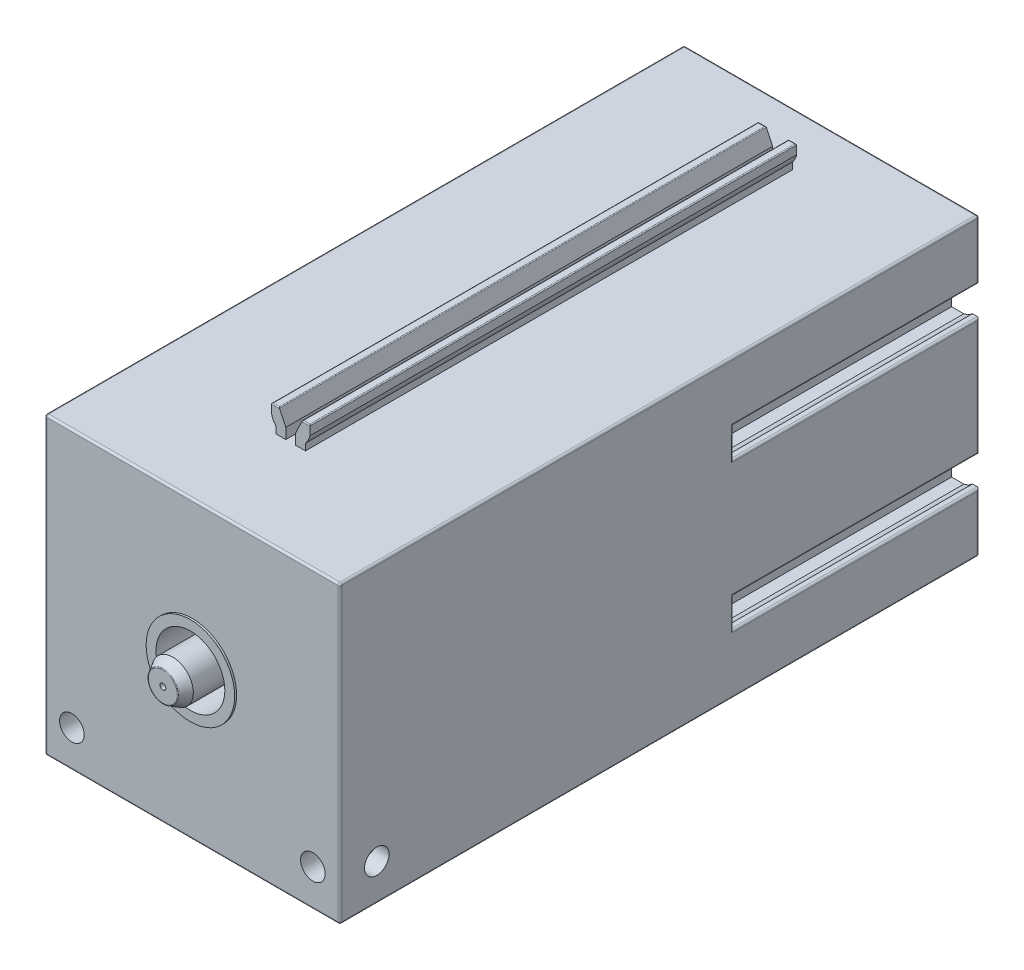
SolidWorks part; units mm, degrees
ref_plane "前视基准面" through (0, 0, 0) normal (0, 0, 1) x (1, 0, 0)
ref_plane "上视基准面" through (0, 0, 0) normal (0, 1, 0) x (1, 0, 0)
ref_plane "右视基准面" through (0, 0, 0) normal (1, 0, 0) x (0, 0, -1)
sketch "草图1" plane through (0, 0, 0) normal (0, 0, 1) x (1, 0, 0)
  line L1 (-15, 0) -> (15, 0)
  line L2 (-15, 0) -> (-15, 30)
  line L3 (-15, 30) -> (15, 30)
  line L4 (15, 0) -> (15, 30)
extrude "凸台-拉伸1" add sketch "草图1" against normal blind 65
sketch "草图2" plane through (0, 0, -65) normal (0, 0, -1) x (-1, 0, 0)
  line L0 (-9, 0.6771) -> (-9, 0)
  line L1 (15, 0) -> (-15, 0) construction
  line L2 (0, -2.0675) -> (0, 3.9748) construction
  line L3 (-6, 0.6771) -> (-6, 0)
  line L4 (-6, 0) -> (-9, 0)
  line L5 (-9.45, 2.8) -> (-5.55, 2.8)
  line L6 (-9.45, 2.8) -> (-9.45, 1.5556)
  line L7 (5.55, 2.8) -> (5.55, 1.5556)
  line L8 (-5.55, 2.8) -> (-5.55, 1.5556)
  line L9 (9.45, 2.8) -> (9.45, 1.5556)
  line L10 (9.45, 2.8) -> (5.55, 2.8)
  line L11 (6, 0) -> (9, 0)
  line L12 (6, 0.6771) -> (6, 0)
  line L13 (9, 0.6771) -> (9, 0)
  arc A0 (9.45, 1.5556) -> (9, 0.6771) centre (7.5, 2) cw
  arc A1 (-6, 0.6771) -> (-5.55, 1.5556) centre (-7.5, 2) ccw
  arc A2 (-9.45, 1.5556) -> (-9, 0.6771) centre (-7.5, 2) ccw
  arc A3 (6, 0.6771) -> (5.55, 1.5556) centre (7.5, 2) cw
extrude "切除-拉伸1" cut sketch "草图2" against normal blind 54
sketch "草图3" plane through (0, 0, -65) normal (0, 0, -1) x (-1, 0, 0)
  line L0 (-14.3229, 9) -> (-15, 9)
  line L1 (-15, 0) -> (-15, 30) construction
  line L2 (-15, 6) -> (-14.3229, 6)
  line L3 (-12.2, 9.45) -> (-12.2, 5.55)
  line L4 (-15, 9) -> (-15, 6)
  line L5 (-12.2, 5.55) -> (-13.4444, 5.55)
  line L6 (-12.2, 9.45) -> (-13.4444, 9.45)
  line L8 (-12.2, 20.55) -> (-13.4444, 20.55)
  line L9 (-12.2, 24.45) -> (-13.4444, 24.45)
  line L10 (-15, 21) -> (-15, 24)
  line L11 (-12.2, 20.55) -> (-12.2, 24.45)
  line L12 (-15, 24) -> (-14.3229, 24)
  line L13 (-14.3229, 21) -> (-15, 21)
  line L15 (14.3229, 21) -> (15, 21)
  line L16 (15, 24) -> (14.3229, 24)
  line L17 (12.2, 20.55) -> (12.2, 24.45)
  line L18 (15, 21) -> (15, 24)
  line L19 (12.2, 24.45) -> (13.4444, 24.45)
  line L20 (12.2, 20.55) -> (13.4444, 20.55)
  line L21 (12.2, 9.45) -> (13.4444, 9.45)
  line L22 (12.2, 5.55) -> (13.4444, 5.55)
  line L23 (15, 9) -> (15, 6)
  line L24 (12.2, 9.45) -> (12.2, 5.55)
  line L25 (15, 6) -> (14.3229, 6)
  line L26 (14.3229, 9) -> (15, 9)
  arc A0 (-14.3229, 6) -> (-13.4444, 5.55) centre (-13, 7.5) ccw
  arc A1 (-13.4444, 9.45) -> (-14.3229, 9) centre (-13, 7.5) ccw
  arc A2 (-13.4444, 20.55) -> (-14.3229, 21) centre (-13, 22.5) cw
  arc A3 (-14.3229, 24) -> (-13.4444, 24.45) centre (-13, 22.5) cw
  arc A4 (14.3229, 24) -> (13.4444, 24.45) centre (13, 22.5) ccw
  arc A5 (13.4444, 20.55) -> (14.3229, 21) centre (13, 22.5) ccw
  arc A6 (13.4444, 9.45) -> (14.3229, 9) centre (13, 7.5) cw
  arc A7 (14.3229, 6) -> (13.4444, 5.55) centre (13, 7.5) cw
extrude "切除-拉伸2" cut sketch "草图3" against normal blind 25
sketch "草图5" plane through (0, 0, -65) normal (0, 0, -1) x (-1, 0, 0)
  line L0 (-1.5, 30.6771) -> (-1.5, 30)
  line L1 (-15, 30) -> (15, 30) construction
  line L2 (1.5, 30) -> (1.5, 30.6771)
  line L3 (-1.95, 32.5) -> (-1.1658, 32.5)
  line L4 (-1.95, 32.5) -> (-1.95, 31.5556)
  line L5 (1.95, 32.5) -> (1.95, 31.5556)
  line L6 (-1.5, 30) -> (-0.5, 30)
  line L7 (-0.5, 30) -> (-0.5, 31.0723)
  line L8 (0.5, 30) -> (0.5, 31.0723)
  line L9 (-0.5, 31.0723) -> (-1.1658, 32.5)
  line L10 (0.5, 31.0723) -> (1.1658, 32.5)
  line L11 (1.1658, 32.5) -> (1.95, 32.5)
  line L12 (0.5, 30) -> (1.5, 30)
  arc A1 (-1.95, 31.5556) -> (-1.5, 30.6771) centre (0, 32) ccw
  arc A2 (1.5, 30.6771) -> (1.95, 31.5556) centre (0, 32) ccw
extrude "凸台-拉伸2" add sketch "草图5" against normal blind 49.5 from offset 5.5 offset against normal yes
fillet "圆角1" radius 0.1 8 edges at (-1.1658, 32.5, -34.75) (-1.5579, 32.5, -10) (-1.95, 32.5, -34.75) (-1.5579, 32.5, -59.5) (1.95, 32.5, -34.75) (1.5579, 32.5, -10) (1.1658, 32.5, -34.75) (1.5579, 32.5, -59.5)
sketch "草图6" plane through (0, 0, 0) normal (0, 0, 1) x (1, 0, 0)
  circle A0 centre (0, 15) radius 3.5
extrude "切除-拉伸3" cut sketch "草图6" against normal blind 5
sketch "草图7" plane through (0, 0, 0) normal (0, 0, 1) x (1, 0, 0)
  circle A0 centre (0, 15) radius 4.5
  circle A1 centre (0, 15) radius 3.5
extrude "凸台-拉伸3" add sketch "草图7" along normal blind 0.2
sketch "草图8" plane through (0, 0, -5) normal (0, 0, 1) x (1, 0, 0)
  circle A0 centre (0, 15) radius 2.1
extrude "凸台-拉伸4" add sketch "草图8" along normal blind 8
sketch "草图9" plane through (0, 0, 3) normal (0, 0, 1) x (1, 0, 0)
  circle A0 centre (0, 15) radius 0.3
extrude "切除-拉伸4" cut sketch "草图9" against normal blind 8
chamfer "倒角1" distance 1 angle 30 1 edges at (2.1, 15, 3) first distance on face at (2.1, 15, 3)
fillet "圆角2" radius 0.1 1 edges at (1.5226, 15, 3)
fillet "圆角3" radius 0.2 36 edges at (-12, 0, -65) (0, 0, 0) (12, 0, -65) (9, 0, -38) (7.5, 0, -11) (6, 0, -38) (0, 0, -65) (-6, 0, -38) (-7.5, 0, -11) (-9, 0, -38) (-15, 15, -65) (-15, 21, -52.5) (-15, 22.5, -40) (-15, 24, -52.5) (-15, 27, -65) (-15, 30, -32.5) (-15, 15, 0) (-15, 0, -32.5) (-15, 3, -65) (-15, 6, -52.5) (-15, 7.5, -40) (-15, 9, -52.5) (15, 15, -65) (15, 9, -52.5) (15, 7.5, -40) (15, 6, -52.5) (15, 3, -65) (15, 0, -32.5) (15, 15, 0) (15, 30, -32.5) (15, 27, -65) (15, 24, -52.5) (15, 22.5, -40) (15, 21, -52.5) (0, 30, -65) (0, 30, 0)
sketch "草图10" plane through (0, 0, 0) normal (0, 0, 1) x (1, 0, 0)
  circle A0 centre (-12.25, 3.75) radius 1.25
  circle A1 centre (12.25, 3.75) radius 1.25
extrude "切除-拉伸5" cut sketch "草图10" against normal blind 5
sketch "草图11" plane through (15, 0, 0) normal (1, 0, 0) x (0, 0, -1)
  circle A0 centre (3.75, 3.75) radius 1.25
extrude "切除-拉伸6" cut sketch "草图11" against normal blind 5
sketch "草图12" plane through (-15, 0, 0) normal (-1, 0, 0) x (0, 0, 1)
  circle A0 centre (-3.75, 3.75) radius 1.25
extrude "切除-拉伸7" cut sketch "草图12" against normal blind 5
